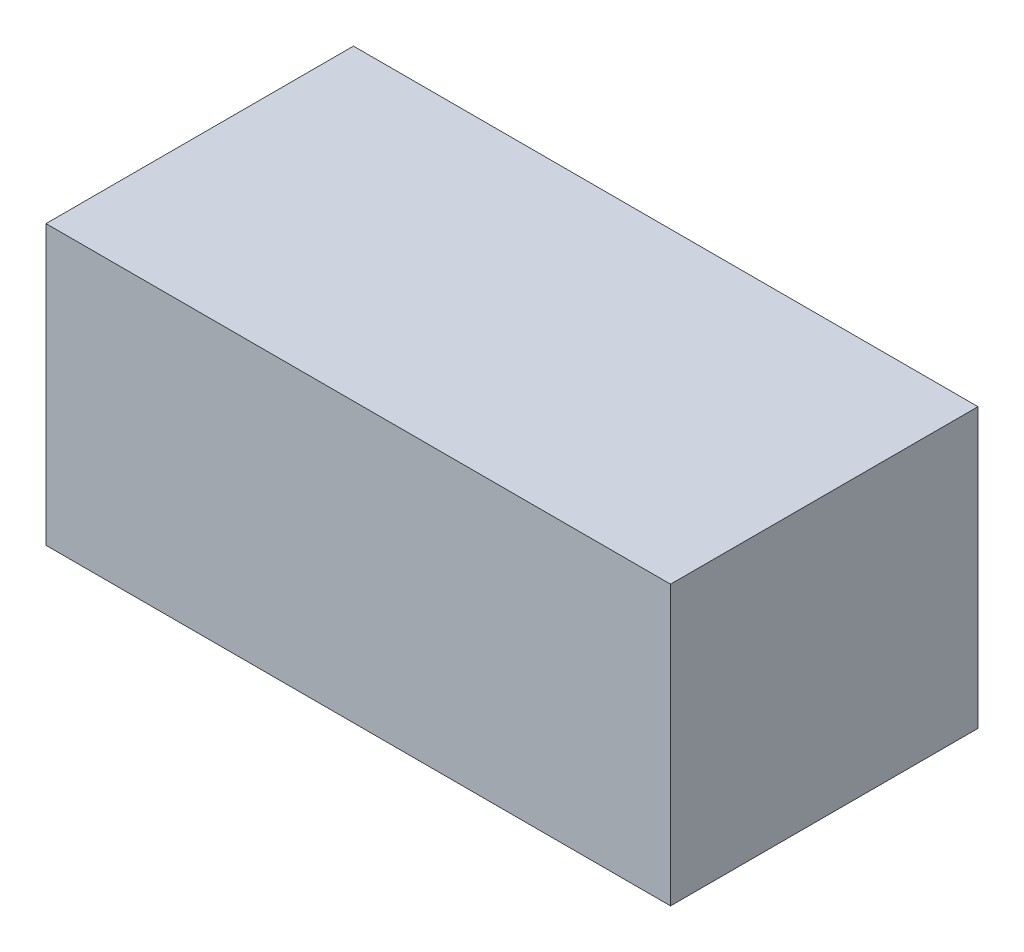
SolidWorks part; units mm, degrees
ref_plane "Front Plane" through (0, 0, 0) normal (0, 0, 1) x (1, 0, 0)
ref_plane "Top Plane" through (0, 0, 0) normal (0, 1, 0) x (1, 0, 0)
ref_plane "Right Plane" through (0, 0, 0) normal (1, 0, 0) x (0, 0, -1)
sketch "Sketch1" plane through (0, 0, 0) normal (0, 1, 0) x (1, 0, 0)
  line L1 (-32.5, 16) -> (32.5, 16)
  line L2 (-32.5, 16) -> (-32.5, -16)
  line L3 (-32.5, -16) -> (32.5, -16)
  line L4 (32.5, 16) -> (32.5, -16)
  line L5 (-32.5, 16) -> (32.5, -16) construction
  line L6 (-32.5, -16) -> (32.5, 16) construction
  point P0 (0, 0)
  dimension "D1" = 65
  dimension "D2" = 32
extrude "Boss-Extrude1" add sketch "Sketch1" along normal mid plane 29
